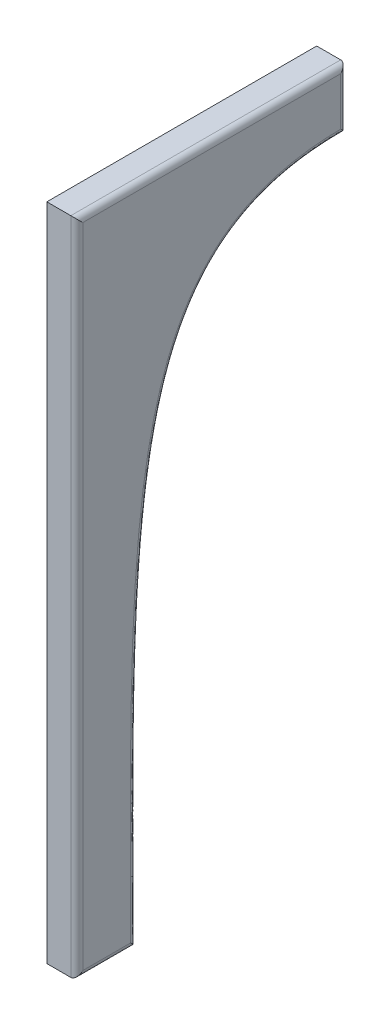
SolidWorks part; units mm, degrees
ref_plane "Front Plane" through (0, 0, 0) normal (0, 0, 1) x (1, 0, 0)
ref_plane "Top Plane" through (0, 0, 0) normal (0, 1, 0) x (1, 0, 0)
ref_plane "Right Plane" through (0, 0, 0) normal (1, 0, 0) x (0, 0, -1)
sketch "Sketch1" plane through (0, 0, 0) normal (1, 0, 0) x (0, 0, -1)
  line L0 (0, 0) -> (0, 279.4)
  line L1 (0, 279.4) -> (114.3, 279.4)
  line L2 (114.3, 279.4) -> (114.3, 254)
  line L3 (0, 0) -> (25.4, 0)
  spline S0 degree 3 poles (25.4, 0) (24.2394, 172.8674) (24.6012, 254.8383) (114.3, 254) knots 0 0 0 0 1 1 1 1
  dimension "D1" = 114.3
  dimension "D2" = 279.4
  dimension "D3" = 25.4
  dimension "D4" = 25.4
extrude "Boss-Extrude1" add sketch "Sketch1" along normal blind 12.7
fillet "Fillet1" radius 2.54 5 edges at (12.7, 266.7, -114.3) (12.7, 0, -12.7) (12.7, 139.7, 0) (12.7, 279.4, -57.15)
